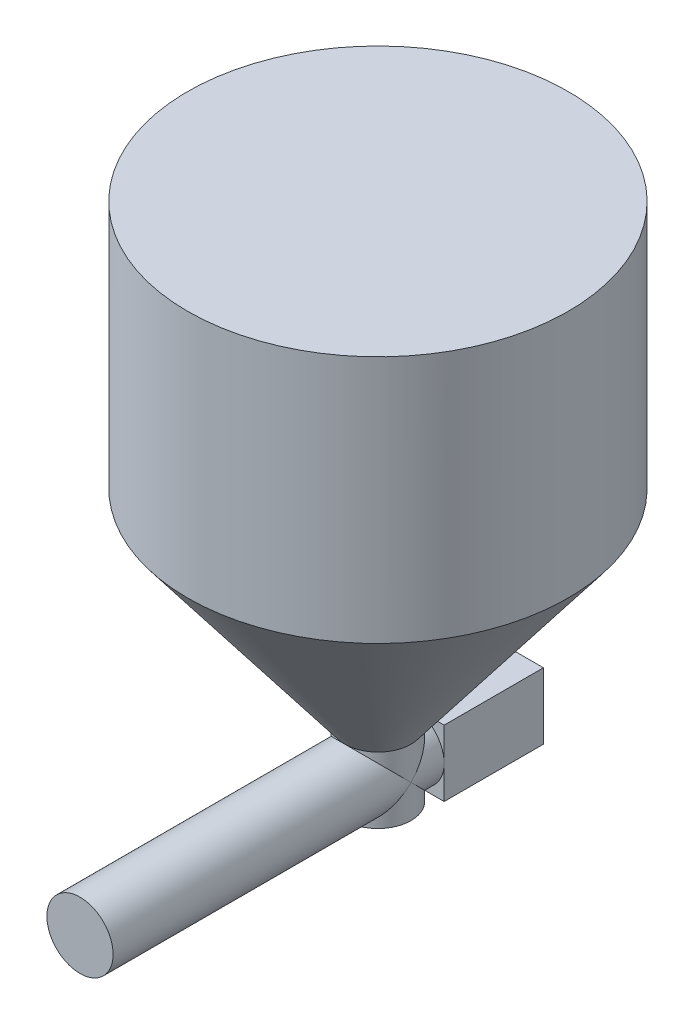
SolidWorks part; units mm, degrees
ref_plane "Alzado" through (0, 0, 0) normal (0, 0, 1) x (1, 0, 0)
ref_plane "Planta" through (0, 0, 0) normal (0, 1, 0) x (1, 0, 0)
ref_plane "Vista lateral" through (0, 0, 0) normal (1, 0, 0) x (0, 0, -1)
sketch "Croquis1" plane through (0, 0, 0) normal (0, 1, 0) x (1, 0, 0)
  circle A0 centre (0, 0) radius 115
  dimension "D1" = 230
ref_plane "Plano1" through (0, -274, 0) normal (0, 1, 0) x (1, 0, 0)
extrude "Saliente-Extruir1" add sketch "Croquis1" against normal blind 150 contours A0
sketch "Croquis2" plane through (0, -150, 0) normal (0, -1, 0) x (1, 0, 0)
  circle A1 centre (0, 0) radius 115
sketch "Croquis3" plane through (0, -274, 0) normal (0, 1, 0) x (1, 0, 0)
  circle A0 centre (0, 0) radius 20
  dimension "D1" = 40
loft "Recubrir1" add profiles "Croquis3", "Croquis2" connector at (-19.9701, -274, 1.0927) connector at (-114.7731, -150, 7.2209)
sketch "Croquis4" plane through (0, -274, 0) normal (0, -1, 0) x (1, 0, 0)
  circle A0 centre (0, 0) radius 20
  dimension "D1" = 40
extrude "Saliente-Extruir2" add sketch "Croquis4" along normal blind 40
ref_plane "Plano2" through (0, 0, -20) normal (0, 0, -1) x (-1, 0, 0)
sketch "Croquis5" plane through (0, 0, -20) normal (0, 0, -1) x (-1, 0, 0)
  line L0 (-20, -314) -> (20, -314) construction
  line L3 (0, -314) -> (0, -274) construction
  line L4 (126.5, -274) -> (-126.5, -274) construction
  circle A0 centre (0, -294) radius 20
  dimension "D1" = 40
extrude "Saliente-Extruir3" add sketch "Croquis5" against normal blind 200
sketch "Croquis6" plane through (0, 0, -20) normal (0, 0, -1) x (-1, 0, 0)
  line L0 (-20, -294) -> (20, -294) construction
  line L2 (-20, -274) -> (20, -274)
  line L3 (-20, -274) -> (-20, -314)
  line L4 (-20, -314) -> (20, -314)
  line L5 (20, -274) -> (20, -314)
  line L6 (-20, -274) -> (20, -314) construction
  line L7 (-20, -314) -> (20, -274) construction
  arc A0 (0, -274) -> (0, -314) centre (0, -294) ccw construction
  arc A1 (0, -314) -> (0, -274) centre (0, -294) ccw construction
  point P8 (0, -294)
  dimension "D1" = 40
  dimension "D2" = 40
extrude "Saliente-Extruir4" add sketch "Croquis6" along normal blind 60
